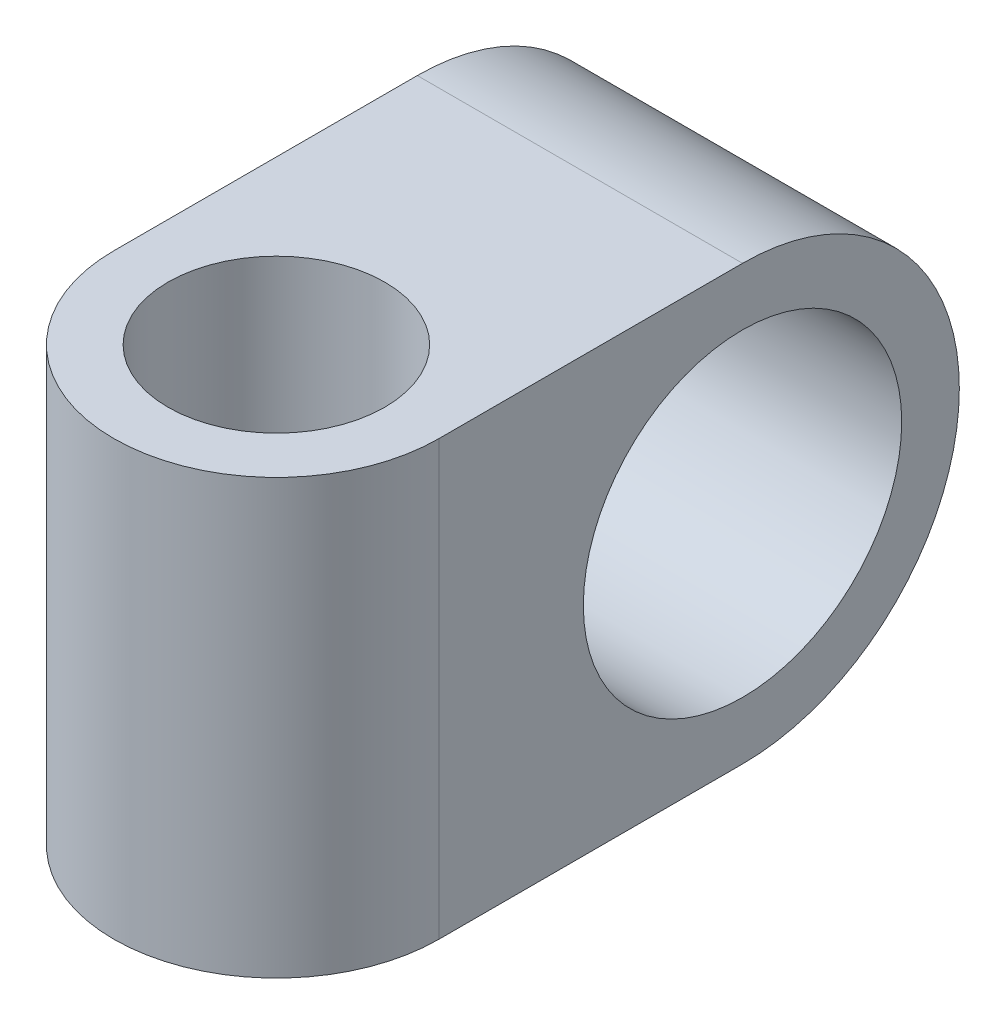
SolidWorks part; units mm, degrees
material "AISI 1020 Steel, Cold Rolled"
ref_plane "Front Plane" through (0, 0, 0) normal (0, 0, 1) x (1, 0, 0)
ref_plane "Top Plane" through (0, 0, 0) normal (0, 1, 0) x (1, 0, 0)
ref_plane "Right Plane" through (0, 0, 0) normal (1, 0, 0) x (0, 0, -1)
sketch "Sketch1" plane through (0, 0, 0) normal (0, 0, 1) x (1, 0, 0)
  line L1 (-11, 11) -> (11, 11)
  line L2 (-11, 11) -> (-11, -11)
  line L3 (-11, -11) -> (11, -11)
  line L4 (11, 11) -> (11, -11)
  line L5 (-11, 11) -> (11, -11) construction
  line L6 (-11, -11) -> (11, 11) construction
  point P0 (0, 0)
  dimension "D1" = 22
  dimension "D2" = 22
extrude "Extrude1" add sketch "Sketch1" along normal blind 40
sketch "Sketch2" plane through (0, 0, 0) normal (1, 0, 0) x (0, 0, -1)
  line L1 (-11, -10) -> (-49.4204, -10)
  line L2 (-49.4204, -10) -> (-49.4204, -16.8874)
  line L3 (-11, 23.0464) -> (8.6162, 23.0464)
  line L4 (8.6162, 23.0464) -> (8.6162, -16.8874)
  line L5 (8.6162, -16.8874) -> (-11, -16.8874)
  line L6 (-49.4204, -16.8874) -> (-11, -16.8874)
  line L14 (-11, 10) -> (-49.4204, 10)
  line L15 (-49.4204, 10) -> (-49.4204, 23.0464)
  line L16 (-49.4204, 23.0464) -> (-11, 23.0464)
  circle A0 centre (-11, 0) radius 7.342 construction
  arc A1 (-11, 10) -> (-11, -10) centre (-11, 0) cw
  dimension "D1" = 14.684
  dimension "D2" = 20
  dimension "D3" = 2.658
  dimension "D5" = 11
extrude "Extrude2" cut sketch "Sketch2" against normal through all and the other way through all
sketch "Sketch3" plane through (0, 0, 0) normal (0, 1, 0) x (1, 0, 0)
  line L0 (-18.8445, 6.8476) -> (-7.5, 6.8476)
  line L1 (-7.5, 6.8476) -> (-7.5, -25)
  line L2 (7.5, -25) -> (7.5, 6.8476)
  line L3 (7.5, 6.8476) -> (23.3089, 6.8476)
  line L4 (-18.8445, 6.8476) -> (-18.8445, -44.3302)
  line L5 (-18.8445, -44.3302) -> (23.3089, -44.3302)
  line L6 (23.3089, -44.3302) -> (23.3089, 6.8476)
  line L7 (0, -3.658) -> (0, -18.342) construction
  circle A0 centre (0, -25) radius 5
  arc A1 (-7.5, -25) -> (7.5, -25) centre (0, -25) ccw
  point P10 (0, -11)
  dimension "D1" = 10
  dimension "D2" = 2.5
  dimension "D3" = 14
extrude "Extrude3" cut sketch "Sketch3" against normal through all and the other way through all
sketch "Sketch6" plane through (7.5, 0, 0) normal (1, 0, 0) x (0, 0, -1)
  point P0 (-11, 0)
hole_wizard "5/8-18 Tapped Hole1" positions "Sketch8" profile "Sketch7" tap size "5/8-18" standard "ANSI Inch" end condition through all
sketch "Sketch8" plane through (7.5, 0, 0) normal (1, 0, 0) x (0, 0, -1)
  point P0 (-11, 0)
sketch "Sketch7" plane through (7.5, 0, 11) normal (0, 1, 0) x (0, 0, -1)
  line L0 (0, 0) -> (0, 15)
  line L1 (0, 15) -> (7.3419, 15)
  line L2 (7.3419, 15) -> (7.3419, 0)
  line L5 (7.3419, 0) -> (0, 0)
  line L11 (0, -6.35) -> (0, 107.95) construction
  dimension "Thru Tap Drill Dia." = 14.6837
  dimension "Thru Tap Drill Depth" = 15
cosmetic thread "Hole Thread1" parameters "D2"=15.875
fillet "Fillet1" [suppressed] radius 0.5
sketch "Sketch4" [suppressed] plane through (0, 0, 0) normal (0, 1, 0) x (1, 0, 0)
  circle A0 centre (0, -25) radius 5
  circle A2 centre (0, -25) radius 5 construction
extrude "Boss-Extrude1" [suppressed] add sketch "Sketch4" along normal blind 15 and the other way blind 14 separate body
sketch "Sketch5" [suppressed] plane through (0, 0, 0) normal (1, 0, 0) x (0, 0, -1)
  circle A0 centre (-11, 0) radius 7.9375
  circle A1 centre (-11, 0) radius 7.9375 construction
extrude "Boss-Extrude2" [suppressed] add sketch "Sketch5" along normal blind 15 and the other way blind 15 separate body
